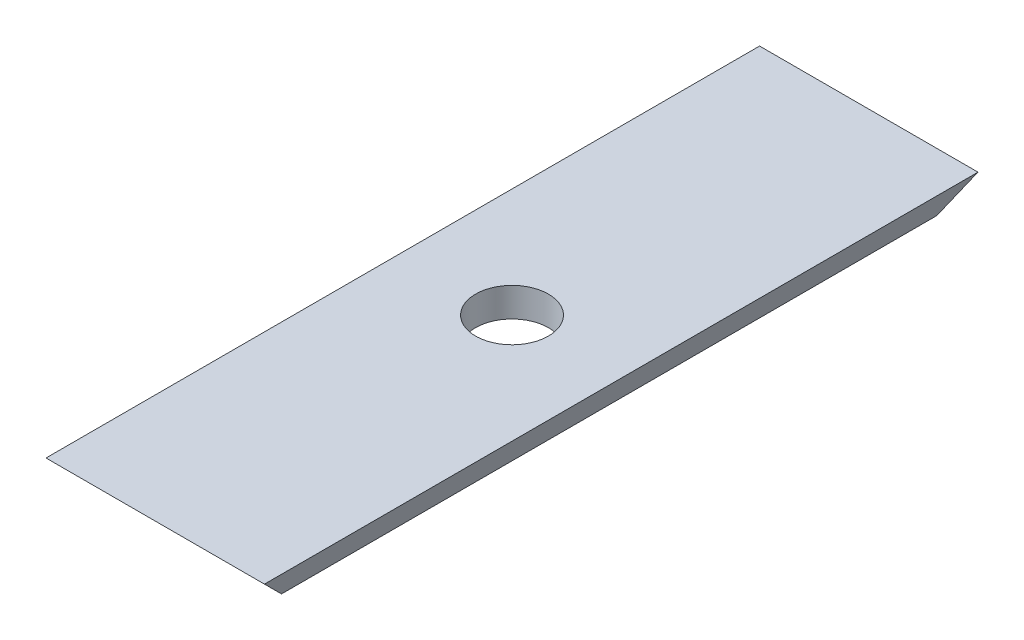
SolidWorks part; units mm, degrees
ref_plane "Plano frontal" through (0, 0, 0) normal (0, 0, 1) x (1, 0, 0)
ref_plane "Plano superior" through (0, 0, 0) normal (0, 1, 0) x (1, 0, 0)
ref_plane "Plano direito" through (0, 0, 0) normal (1, 0, 0) x (0, 0, -1)
sketch "Esboço1" plane through (0, 0, 0) normal (0, 0, 1) x (1, 0, 0)
  line L1 (0, 0) -> (150, 0)
  line L2 (0, 0) -> (0, 20)
  line L3 (0, 20) -> (150, 20)
  line L4 (150, 0) -> (150, 20)
  dimension "D1" = 150
  dimension "D2" = 20
extrude "Ressalto-extrusão1" add sketch "Esboço1" along normal blind 490
chamfer "Chanfro1" distance 20 angle 45 3 edges at (75, 0, 490) (0, 0, 245) (75, 0, 0)
sketch "Esboço2" plane through (0, 0, 0) normal (0, -1, 0) x (-1, 0, 0)
  line L0 (0, -490) -> (0, 0) construction
  line L1 (-150, 0) -> (0, 0) construction
  circle A0 centre (-75, -245) radius 25
  dimension "D1" = 50
  dimension "D2" = 75
  dimension "D3" = 245
extrude "Corte-extrusão1" cut sketch "Esboço2" against normal through all
chamfer "Chanfro2" distance 20 angle 22.5 1 edges at (150, 0, 245) first distance on face at (150, 10, 245)
